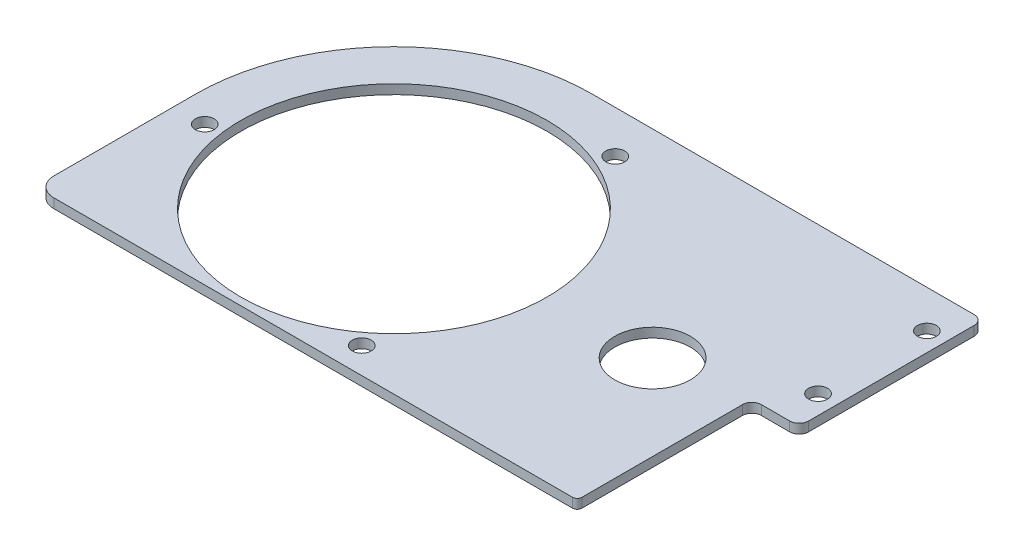
SolidWorks part; units mm, degrees
ref_plane "Front Plane" through (0, 0, 0) normal (0, 0, 1) x (1, 0, 0)
ref_plane "Top Plane" through (0, 0, 0) normal (0, 1, 0) x (1, 0, 0)
ref_plane "Right Plane" through (0, 0, 0) normal (1, 0, 0) x (0, 0, -1)
sketch "Sketch1" plane through (0, 0, 0) normal (0, 1, 0) x (1, 0, 0)
  line L0 (0, 114.3) -> (0, -101.6) construction
  line L1 (256.5211, 133.3689) -> (0, 133.3689)
  line L2 (262.8711, 127.0189) -> (262.8711, 15.8008)
  line L3 (227.9555, -107.9311) -> (-120.6689, -107.9311)
  line L4 (-133.3689, 0) -> (-133.3689, -95.2311)
  line L5 (237.4711, 9.4508) -> (256.5211, 9.4508)
  line L6 (250.1711, 9.4508) -> (250.1711, 133.3689) construction
  line L7 (0, 0) -> (-133.3689, 0) construction
  line L8 (0, 0) -> (-133.3689, -3.0078) construction
  line L11 (231.1211, -104.7655) -> (231.1211, 3.1008)
  circle A0 centre (0, 0) radius 102.87
  circle A1 centre (0, 0) radius 114.3 construction
  circle A2 centre (-112.7386, -14.375) radius 6.35
  arc A3 (237.4711, 9.4508) -> (231.1211, 3.1008) centre (237.4711, 3.1008) ccw
  arc A4 (-133.3689, 0) -> (0, 133.3689) centre (0, 0) cw
  circle A5 centre (43.9202, 104.822) radius 6.35
  circle A6 centre (68.8184, -90.447) radius 6.35
  arc A7 (-120.6689, -107.9311) -> (-133.3689, -95.2311) centre (-120.6689, -95.2311) cw
  arc A8 (227.9555, -107.9311) -> (231.1211, -104.7655) centre (227.9555, -104.7655) ccw
  arc A9 (262.8711, 15.8008) -> (256.5211, 9.4508) centre (256.5211, 15.8008) cw
  arc A10 (256.5211, 133.3689) -> (262.8711, 127.0189) centre (256.5211, 127.0189) cw
  circle A11 centre (250.1711, 107.9689) radius 6.35
  circle A12 centre (250.1711, 34.8508) radius 6.35
  circle A13 centre (-112.7386, -14.375) radius 6.35 construction
  point P0 (0, 0)
  point P11 (0, 0)
  point P12 (246.9961, 9.4508)
  point P32 (231.1211, -107.9311)
  point P46 (0, 0)
  dimension "D3" = 205.74
  dimension "D5" = 228.6
  dimension "D6" = 12.7
  dimension "D7" = 123.9181
  dimension "D8" = 133.3689
  dimension "D11" = 31.75
  dimension "D12" = 25.4
  dimension "D14" = 12.7
  dimension "D9" = 6.35
  dimension "D10" = 12.7
  dimension "D2" = 117.3819
  dimension "D4" = 113.6514
  dimension "D13" = 12.7
  dimension "D15" = 25.4
  dimension "D16" = 396.24
  dimension "D17" = 3
extrude "Boss-Extrude1" add sketch "Sketch1" along normal blind 6.35
sketch "Sketch3" plane through (0, 6.35, 0) normal (0, 1, 0) x (1, 0, 0)
  line L0 (73.0061, 133.3689) -> (73.0061, -107.9311) construction
  line L5 (382.3904, 12.7189) -> (-202.4477, 12.7189) construction
  line L6 (333.3561, -152.3811) -> (-187.3439, -152.3811)
  line L7 (333.3561, -152.3811) -> (333.3561, 177.8189)
  line L8 (333.3561, 177.8189) -> (-187.3439, 177.8189)
  line L9 (-187.3439, -152.3811) -> (-187.3439, 177.8189)
  line L10 (333.3561, -152.3811) -> (-187.3439, 177.8189) construction
  line L11 (333.3561, 177.8189) -> (-187.3439, -152.3811) construction
  line L26 (262.8711, 15.8008) -> (262.8711, 127.0189) construction
  line L27 (-133.3689, 0) -> (-133.3689, -95.2311) construction
  line L28 (-120.6689, -107.9311) -> (227.9555, -107.9311) construction
  line L29 (256.5211, 133.3689) -> (0, 133.3689) construction
  line L30 (262.8711, 15.8008) -> (262.8711, 127.0189)
  line L31 (-133.3689, 0) -> (-133.3689, -95.2311)
  line L32 (-120.6689, -107.9311) -> (227.9555, -107.9311)
  line L33 (256.5211, 133.3689) -> (0, 133.3689)
  point P1 (73.0061, 12.7189)
  dimension "D1" = 520.7
  dimension "D2" = 206.375
  dimension "D3" = 330.2
  dimension "D4" = 120.65
  dimension "D7" = 396.24
  dimension "D8" = 241.3
sketch "Sketch5" plane through (0, 0, 0) normal (0, 1, 0) x (1, 0, 0)
  line L0 (0, 0) -> (198.4659, 6.2838) construction
  line L1 (209.8959, 6.2531) -> (187.0359, 6.3145) construction
  circle A1 centre (161.2021, 5.104) radius 11.176 construction
sketch "Sketch6" plane through (0, 0, 0) normal (0, 1, 0) x (1, 0, 0)
  line L0 (6.35, 0) -> (5.207, 0) construction
  line L1 (0, 0) -> (229.3291, 0) construction
  circle A0 centre (173.8109, 0) radius 25.4
  circle A1 centre (0, 0) radius 6.35 construction
  circle A2 centre (0, 0) radius 5.207 construction
  point P7 (0, 0)
  point P8 (0, 0)
  dimension "D1" = 50.8
extrude "Cut-Extrude1" cut sketch "Sketch6" along normal blind 28.448
